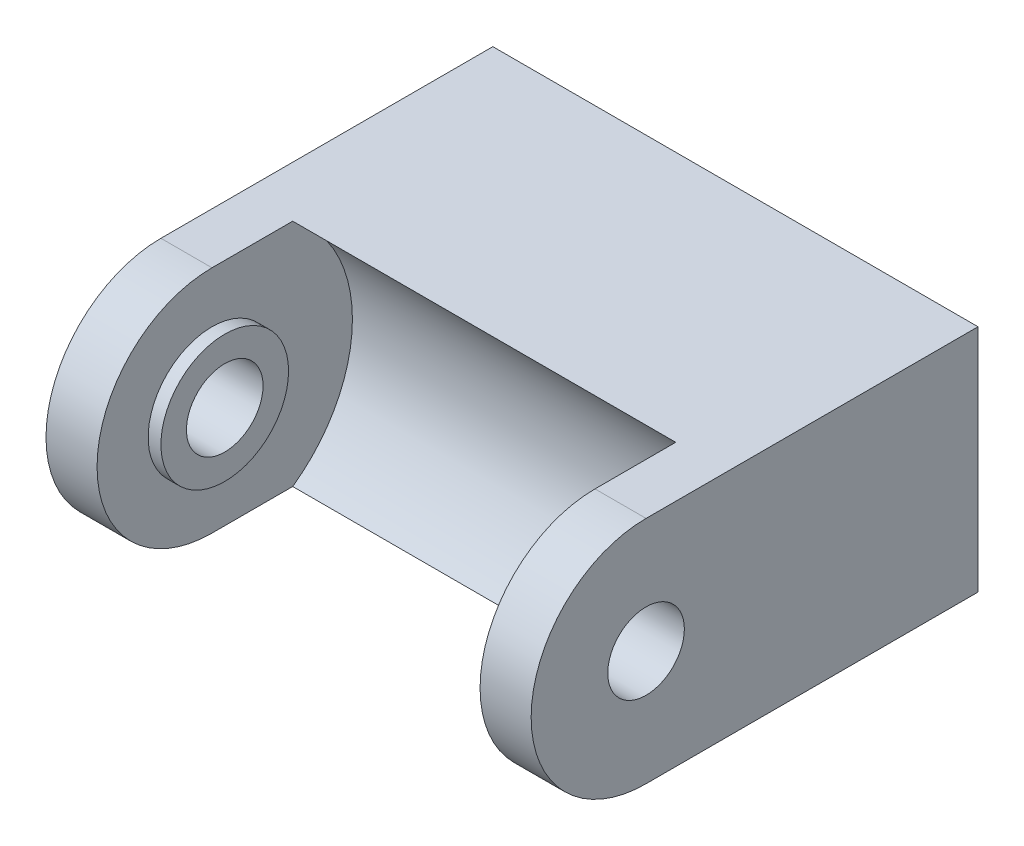
SolidWorks part; units mm, degrees
ref_plane "Front" through (0, 0, 0) normal (0, 0, 1) x (1, 0, 0)
ref_plane "Top" through (0, 0, 0) normal (0, 1, 0) x (1, 0, 0)
ref_plane "Right" through (0, 0, 0) normal (1, 0, 0) x (0, 0, -1)
sketch "Эскиз1" plane through (0, 0, 0) normal (1, 0, 0) x (0, 0, -1)
  line L0 (0, 4.5) -> (13, 4.5)
  line L1 (13, 4.5) -> (13, -4.5)
  line L2 (13, -4.5) -> (0, -4.5)
  circle A0 centre (0, 0) radius 4.5
  dimension "D1" = 9
  dimension "D2" = 13
extrude "Бобышка-Вытянуть1" add sketch "Эскиз1" along normal blind 9.5 and the other way blind 9.5 contours A0 | A0 L2 L1 L0 region at (0, 0, -8.2139) region at (0, 0, 0)
sketch "Эскиз2" plane through (0, 0, 0) normal (1, 0, 0) x (0, 0, -1)
  circle A0 centre (0, 0) radius 5.5
extrude "Вырез-Вытянуть1" cut sketch "Эскиз2" against normal blind 7 and the other way blind 7
sketch "Эскиз3" plane through (0, 0, 0) normal (1, 0, 0) x (0, 0, -1)
  circle A0 centre (0, 0) radius 1.5
extrude "Вырез-Вытянуть2" cut sketch "Эскиз3" against normal through all both and the other way through all
sketch "Эскиз4" plane through (0, 0, 0) normal (1, 0, 0) x (0, 0, -1)
  circle A0 centre (0, 0) radius 5.5
  circle A1 centre (0, 0) radius 2.5
  dimension "D1" = 5
  dimension "D2" = 11
extrude "Вырез-Вытянуть3" cut sketch "Эскиз4" against normal blind 7.5 and the other way blind 7.5
sketch "Эскиз5" plane through (0, 0, -13) normal (0, 0, -1) x (-1, 0, 0)
  circle A0 centre (0, 0) radius 1.75
extrude "Вырез-Вытянуть4" cut sketch "Эскиз5" against normal blind 2
